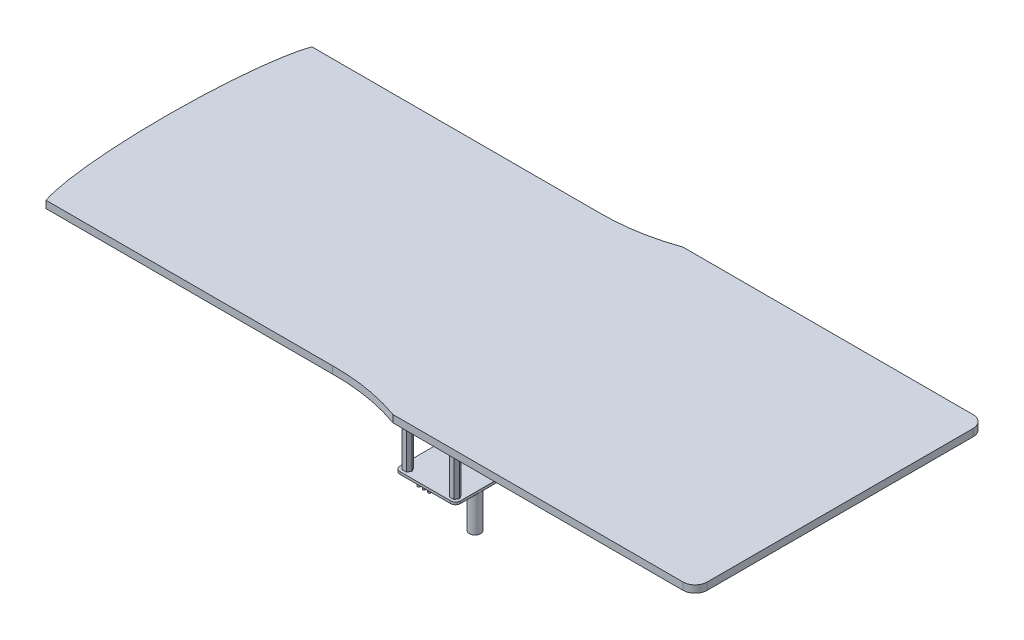
SolidWorks part; units mm, degrees
ref_plane "정면" through (0, 0, 0) normal (0, 0, 1) x (1, 0, 0)
ref_plane "윗면" through (0, 0, 0) normal (0, 1, 0) x (1, 0, 0)
ref_plane "우측면" through (0, 0, 0) normal (1, 0, 0) x (0, 0, -1)
sketch "스케치1" plane through (0, 0, 0) normal (0, 1, 0) x (1, 0, 0)
  line L1 (-140, 60) -> (140, 60)
  line L2 (-140, 60) -> (-140, -60)
  line L3 (-140, -60) -> (140, -60)
  line L4 (140, 60) -> (140, -60)
  line L5 (-140, 60) -> (140, -60) construction
  line L6 (-140, -60) -> (140, 60) construction
  point P0 (0, 0)
  dimension "D1" = 280
  dimension "D2" = 120
extrude "보스-돌출1" add sketch "스케치1" along normal blind 3
sketch "스케치2" plane through (0, 3, 0) normal (0, 1, 0) x (1, 0, 0)
  line L0 (-140, 60) -> (-130, 60)
  line L1 (140, 60) -> (-140, 60) construction
  line L2 (-130, 60) -> (-130, -60) construction
  line L3 (-140, -60) -> (140, -60) construction
  line L4 (-140, 60) -> (-140, 0)
  line L5 (-140, 0) -> (-140, -60)
  line L6 (-140, -60) -> (-130, -60)
  ellipse E0 centre (-130, 0) end of major axis (-130, -60) minor radius 9
  line M2 (140, 60) -> (-140, 60)
  line M3 (-140, 60) -> (-140, -60)
  line M4 (-140, -60) -> (140, -60)
  dimension "D1" = 10
  dimension "D2" = 9
extrude "컷-돌출1" cut sketch "스케치2" against normal blind 3 contours E0 M2 M3 M4 region at (-135, 3, -58.7958)
sketch "스케치3" plane through (0, 3, 0) normal (0, 1, 0) x (1, 0, 0)
  line L0 (140, 60) -> (-130, 60) construction
  line L1 (140, -60) -> (15, -60)
  line L2 (140, -60) -> (140, 60)
  line L3 (140, 60) -> (15, 60)
  line L4 (15, -60) -> (15, 60)
  line L5 (140, 0) -> (-65.3551, 0) construction
  line L6 (15, -60) -> (-15, -60)
  line L7 (-130, -60) -> (140, -60) construction
  line L8 (15, 60) -> (-15, 60)
  line L9 (-15, -60) -> (-15, -55)
  line L10 (-15, 60) -> (-15, 55)
  line L11 (-15, -55) -> (-133.5969, -55)
  line L12 (-15, 55) -> (-133.5969, 55)
  ellipse E0 centre (-130, 0) end of major axis (-130, -60) minor radius 9 (-130, 60) -> (-130, -60) ccw construction
  spline S0 degree 2 poles (-15, 55) (0.4381, 54.8504) (15, 60) knots 0 0 0 1 1 1
  spline S1 degree 2 poles (-15, -55) (0.4381, -54.8504) (15, -60) knots 0 0 0 1 1 1
  line M6 (140, 60) -> (-130, 60)
  ellipse M7 centre (-130, 0) end of major axis (-130, -60) minor radius 9 (-130, 60) -> (-130, -60) ccw
  line M8 (-130, -60) -> (140, -60)
  dimension "D1" = 125
  dimension "D2" = 30
  dimension "D3" = 5
extrude "컷-돌출2" cut sketch "스케치3" against normal blind 3 contours L9 L11 M7 M8 | L12 L10 M6 M7 region at (-73.7124, 3, 57.4899) region at (-73.7124, 3, -57.4899)
extrude "컷-돌출3" cut sketch "스케치3<4>" against normal blind 3 contours L10 S0 M6 | S1 L9 M8 region at (-3.645, 3, 57.9703) region at (-3.645, 3, -57.9703)
sketch "스케치3<4>" plane through (0, 3, 0) normal (0, 1, 0) x (1, 0, 0) same geometry as "스케치3"
sketch "스케치4" plane through (0, 3, 0) normal (0, 1, 0) x (1, 0, 0)
  line L0 (140, 0) -> (-139, 0) construction
  line L1 (140, -60) -> (140, 60) construction
  line L2 (140, 60) -> (140, -60)
  line L3 (140, 60) -> (74.6716, 60)
  line L4 (140, 60) -> (15, 60) construction
  line L5 (140, -60) -> (74.6716, -60)
  circle A0 centre (135, 55) radius 5
  circle A1 centre (135, -55) radius 5
  ellipse E0 centre (-130, 0) end of major axis (-130, -60) minor radius 9 (-133.5969, 55) -> (-133.5969, -55) ccw construction
  line M11 (140, -60) -> (140, 60)
  line M12 (140, 60) -> (15, 60)
  dimension "D1" = 10
  dimension "D2" = 10
extrude "컷-돌출4" cut sketch "스케치4" against normal through all contours A0 L2 M12 | A1 L5 M11 region at (138.8832, 3, 58.8832) region at (138.8832, 3, -58.8832)
sketch "스케치5" plane through (-8.1057, 0, 0) normal (0, -1, 0) x (-1, 0, 0)
  line L1 (-14.9611, -51) -> (-39.9611, -51) construction
  line L2 (-14.9611, -51) -> (-14.9611, 10) construction
  line L3 (-14.9611, 10) -> (-39.9611, 10) construction
  line L4 (-39.9611, -51) -> (-39.9611, 10) construction
  line L5 (-27.4611, 10) -> (-27.4611, -51) construction
  line L6 (-16.7613, 8.8734) -> (-15.8952, 7.3734)
  line L7 (-39.027, 7.3734) -> (-38.161, 5.8734)
  line L8 (-38.161, 5.8734) -> (-36.4289, 5.8734)
  line L9 (-36.4289, 5.8734) -> (-35.5629, 7.3734)
  line L10 (-35.5629, 7.3734) -> (-36.4289, 8.8734)
  line L11 (-36.4289, 8.8734) -> (-38.161, 8.8734)
  line L12 (-38.161, 8.8734) -> (-39.027, 7.3734)
  line L13 (-18.4933, 8.8734) -> (-16.7613, 8.8734)
  line L14 (-19.3593, 7.3734) -> (-18.4933, 8.8734)
  line L15 (-18.4933, 5.8734) -> (-19.3593, 7.3734)
  line L16 (-16.7613, 5.8734) -> (-18.4933, 5.8734)
  line L17 (-15.8952, 7.3734) -> (-16.7613, 5.8734)
  line L18 (-39.9611, -20.5) -> (-14.9611, -20.5) construction
  line L19 (-15.8952, -48.3734) -> (-16.7613, -46.8734)
  line L20 (-16.7613, -46.8734) -> (-18.4933, -46.8734)
  line L21 (-18.4933, -46.8734) -> (-19.3593, -48.3734)
  line L22 (-19.3593, -48.3734) -> (-18.4933, -49.8734)
  line L23 (-18.4933, -49.8734) -> (-16.7613, -49.8734)
  line L24 (-38.161, -49.8734) -> (-39.027, -48.3734)
  line L25 (-36.4289, -49.8734) -> (-38.161, -49.8734)
  line L26 (-35.5629, -48.3734) -> (-36.4289, -49.8734)
  line L27 (-36.4289, -46.8734) -> (-35.5629, -48.3734)
  line L28 (-38.161, -46.8734) -> (-36.4289, -46.8734)
  line L29 (-39.027, -48.3734) -> (-38.161, -46.8734)
  line L30 (-16.7613, -49.8734) -> (-15.8952, -48.3734)
  circle A0 centre (-37.2949, 7.3734) radius 1.5 construction
  circle A1 centre (-17.6273, 7.3734) radius 1.5 construction
  circle A2 centre (-17.6273, -48.3734) radius 1.5 construction
  circle A3 centre (-37.2949, -48.3734) radius 1.5 construction
  dimension "D4" = 3
  dimension "D1" = 25
  dimension "D2" = 61
extrude "보스-돌출2" add sketch "스케치5" along normal blind 25
sketch "스케치6" plane through (-8.1057, -25, 0) normal (0, -1, 0) x (1, 0, 0)
  line L1 (14.9611, 51) -> (39.9611, 51)
  line L2 (14.9611, 51) -> (14.9611, -10)
  line L3 (14.9611, -10) -> (39.9611, -10)
  line L4 (39.9611, 51) -> (39.9611, -10)
extrude "보스-돌출3" add sketch "스케치6" along normal blind 1
sketch "스케치7" plane through (-8.1057, -26, 0) normal (0, -1, 0) x (1, 0, 0)
  line L0 (14.9611, 51) -> (14.9611, -10) construction
  line L1 (14.9611, 45.5) -> (23.643, 45.5)
  line L2 (14.9611, 45.5) -> (14.9611, -4.5)
  line L3 (14.9611, -4.5) -> (23.643, -4.5)
  line L4 (23.643, 45.5) -> (23.643, -4.5)
  line L5 (14.9611, 51) -> (39.9611, 51) construction
  line L6 (14.9611, -10) -> (39.9611, -10) construction
  dimension "D1" = 5.5
  dimension "D2" = 5.5
extrude "보스-돌출4" add sketch "스케치7" along normal blind 1
sketch "스케치8" plane through (-8.1057, -27, 0) normal (0, -1, 0) x (1, 0, 0)
  line L0 (19.3021, 45.5) -> (19.3021, -4.5) construction
  line L1 (23.643, 45.5) -> (14.9611, 45.5) construction
  line L2 (14.9611, -4.5) -> (23.643, -4.5) construction
  line L4 (23.643, -4.5) -> (23.643, 45.5) construction
  line L5 (14.9611, 18.5) -> (23.643, 18.5)
  line L6 (14.9611, 18.5) -> (14.9611, 22.5)
  line L7 (14.9611, 22.5) -> (23.643, 22.5)
  line L8 (23.643, 18.5) -> (23.643, 22.5)
  line L9 (14.9611, 18.5) -> (23.643, 22.5) construction
  line L10 (14.9611, 22.5) -> (23.643, 18.5) construction
  line L11 (14.9611, 45.5) -> (14.9611, 22.5) construction
  line L12 (23.643, 20.5) -> (14.9611, 20.5) construction
  line L13 (14.9611, 34.75) -> (23.643, 34.75)
  line L14 (14.9611, 34.75) -> (14.9611, 33.25)
  line L15 (14.9611, 33.25) -> (23.643, 33.25)
  line L16 (23.643, 34.75) -> (23.643, 33.25)
  line L17 (14.9611, 34.75) -> (23.643, 33.25) construction
  line L18 (14.9611, 33.25) -> (23.643, 34.75) construction
  line L19 (23.643, 6.25) -> (23.643, 7.75)
  line L20 (14.9611, 6.25) -> (14.9611, 7.75)
  line L21 (14.9611, 6.25) -> (23.643, 6.25)
  line L22 (14.9611, 7.75) -> (23.643, 7.75)
  point P7 (19.3021, 34)
  point P8 (19.3021, 20.5)
  dimension "D1" = 4
  dimension "D2" = 1.5
extrude "컷-돌출5" cut sketch "스케치8" against normal blind 1
sketch "스케치9" plane through (-8.1057, -27, 0) normal (0, -1, 0) x (1, 0, 0)
  line L0 (19.3021, 45.5) -> (19.3021, 34.75) construction
  line L1 (23.643, 45.5) -> (14.9611, 45.5) construction
  line L2 (23.643, 34.75) -> (14.9611, 34.75) construction
  line L3 (14.9611, 45.5) -> (19.3021, 45.5) construction
  line L4 (17.1316, 45.5) -> (17.1316, 34.75) construction
  line L5 (19.4081, 45.5) -> (23.643, 45.5) construction
  line L6 (21.5255, 45.5) -> (21.5255, 34.75) construction
  line L7 (14.9611, 45.5) -> (14.9611, 34.75) construction
  line L8 (14.9611, 43.35) -> (23.643, 43.35) construction
  line L9 (23.643, 34.75) -> (23.643, 45.5) construction
  line L10 (23.643, 41.2) -> (14.9611, 41.2) construction
  line L11 (23.643, 39.05) -> (14.9611, 39.05) construction
  line L12 (23.643, 36.6613) -> (14.9611, 36.6613) construction
  line L13 (23.643, 34.75) -> (23.643, 45.5) construction
  line L14 (14.9611, 34) -> (24.7906, 34) construction
  line L15 (14.9611, 34.75) -> (14.9611, 33.25) construction
  line L16 (14.9611, 20.5) -> (24.7906, 20.5) construction
  line L17 (14.9611, 22.5) -> (14.9611, 18.5) construction
  circle A0 centre (17.1316, 43.35) radius 0.5
  circle A1 centre (19.3021, 43.35) radius 0.5
  circle A2 centre (21.5255, 43.35) radius 0.5
  circle A3 centre (17.1316, 41.2) radius 0.5
  circle A4 centre (19.3021, 41.2) radius 0.5
  circle A5 centre (21.5255, 41.2) radius 0.5
  circle A6 centre (17.1316, 39.05) radius 0.5
  circle A7 centre (19.3021, 39.05) radius 0.5
  circle A8 centre (21.5255, 39.05) radius 0.5
  circle A9 centre (17.1316, 36.6613) radius 0.5
  circle A10 centre (19.3021, 36.6613) radius 0.5
  circle A11 centre (21.5255, 36.6613) radius 0.5
  circle A12 centre (21.5255, 31.3387) radius 0.5
  circle A13 centre (19.3021, 31.3387) radius 0.5
  circle A14 centre (17.1316, 31.3387) radius 0.5
  circle A15 centre (21.5255, 28.95) radius 0.5
  circle A16 centre (19.3021, 28.95) radius 0.5
  circle A17 centre (17.1316, 28.95) radius 0.5
  circle A18 centre (21.5255, 26.8) radius 0.5
  circle A19 centre (19.3021, 26.8) radius 0.5
  circle A20 centre (17.1316, 26.8) radius 0.5
  circle A21 centre (21.5255, 24.65) radius 0.5
  circle A22 centre (19.3021, 24.65) radius 0.5
  circle A23 centre (17.1316, 24.65) radius 0.5
  circle A24 centre (17.1316, 16.35) radius 0.5
  circle A25 centre (19.3021, 16.35) radius 0.5
  circle A26 centre (21.5255, 16.35) radius 0.5
  circle A27 centre (17.1316, 14.2) radius 0.5
  circle A28 centre (19.3021, 14.2) radius 0.5
  circle A29 centre (21.5255, 14.2) radius 0.5
  circle A30 centre (17.1316, 12.05) radius 0.5
  circle A31 centre (19.3021, 12.05) radius 0.5
  circle A32 centre (21.5255, 12.05) radius 0.5
  circle A33 centre (17.1316, 9.6613) radius 0.5
  circle A34 centre (19.3021, 9.6613) radius 0.5
  circle A35 centre (21.5255, 9.6613) radius 0.5
  circle A36 centre (21.5255, 4.3387) radius 0.5
  circle A37 centre (19.3021, 4.3387) radius 0.5
  circle A38 centre (17.1316, 4.3387) radius 0.5
  circle A39 centre (21.5255, 1.95) radius 0.5
  circle A40 centre (19.3021, 1.95) radius 0.5
  circle A41 centre (17.1316, 1.95) radius 0.5
  circle A42 centre (21.5255, -0.2) radius 0.5
  circle A43 centre (19.3021, -0.2) radius 0.5
  circle A44 centre (17.1316, -0.2) radius 0.5
  circle A45 centre (21.5255, -2.35) radius 0.5
  circle A46 centre (19.3021, -2.35) radius 0.5
  circle A47 centre (17.1316, -2.35) radius 0.5
  point P29 (17.1316, 43.35)
  point P30 (17.1316, 41.2)
  point P31 (17.1316, 43.35)
  point P32 (17.1316, 43.35)
  point P33 (17.1316, 39.05)
  point P35 (17.1316, 36.6613)
  point P36 (19.3021, 43.35)
  point P37 (19.3021, 41.2)
  point P38 (19.3021, 39.05)
  point P39 (19.3021, 36.6613)
  point P40 (21.5255, 43.35)
  point P41 (21.5255, 41.2)
  point P42 (21.5255, 39.05)
  point P43 (21.5255, 36.6613)
  point P95 (17.1316, 24.65)
  point P96 (17.1316, 24.65)
  point P149 (17.1316, 16.35)
  point P150 (17.1316, 16.35)
  point P151 (17.1316, -2.35)
  point P152 (17.1316, -2.35)
  dimension "D1" = 2.15
  dimension "D2" = 2.15
  dimension "D3" = 2.15
  dimension "D4" = 2.3887
extrude "보스-돌출5" add sketch "스케치9" along normal blind 7
sketch "스케치10" plane through (-8.1057, -26, 0) normal (0, -1, 0) x (1, 0, 0)
  line L0 (14.9611, 20.5) -> (39.9611, 20.5) construction
  line L1 (14.9611, 22.5) -> (14.9611, 18.5) construction
  line L2 (39.9611, -10) -> (39.9611, 51) construction
  line L3 (27.4611, 51) -> (27.4611, -10) construction
  line L4 (39.9611, 51) -> (14.9611, 51)
  line L5 (39.9611, 51) -> (39.9611, -10)
  line L6 (39.9611, -10) -> (14.9611, -10)
  line L7 (14.9611, 51) -> (14.9611, -10)
  arc A0 (39.9611, 49) -> (37.9611, 51) centre (37.9611, 49) ccw
  arc A1 (14.9611, 49) -> (16.9611, 51) centre (16.9611, 49) cw
  arc A2 (14.9611, -8) -> (16.9611, -10) centre (16.9611, -8) ccw
  arc A3 (39.9611, -8) -> (37.9611, -10) centre (37.9611, -8) cw
  line M21 (14.9611, -10) -> (39.9611, -10)
  line M22 (39.9611, -10) -> (39.9611, 51)
  line M23 (39.9611, 51) -> (14.9611, 51)
  line M24 (14.9611, 51) -> (14.9611, 45.5)
extrude "컷-돌출6" cut sketch "스케치10" against normal blind 7 contours A2 L7 M21 | A3 M22 M21 | A0 L5 M23 | A1 M24 M23 region at (31.4087, -26, 50.5533) region at (7.3022, -26, 50.5533) region at (31.4087, -26, -9.5533) region at (7.3022, -26, -9.5533)
sketch "스케치11" plane through (-8.1057, -26, 0) normal (0, -1, 0) x (1, 0, 0)
  line L0 (23.643, 22.5) -> (39.9611, 22.5) construction
  line L1 (39.9611, -8) -> (39.9611, 49) construction
  line L2 (23.643, 18.5) -> (39.9611, 18.5) construction
  line L4 (39.9611, 22.5) -> (34.9611, 22.5)
  line L5 (39.9611, 22.5) -> (39.9611, 18.5)
  line L6 (39.9611, 18.5) -> (34.9611, 18.5)
  line L7 (34.9611, 22.5) -> (34.9611, 18.5)
  dimension "D1" = 5
extrude "보스-돌출6" add sketch "스케치11" along normal blind 8
sketch "스케치12" plane through (-8.1057, 0, 22.5) normal (0, 0, 1) x (1, 0, 0)
  line L0 (37.4611, -34) -> (37.4611, -26) construction
  line L1 (39.9611, -34) -> (34.9611, -34) construction
  line L2 (39.9611, -26) -> (34.9611, -26) construction
  line L3 (36.4492, -34) -> (38.4731, -34)
  line L4 (38.4731, -34) -> (39.9611, -32.359)
  line L5 (39.9611, -34) -> (39.9611, -26) construction
  line L6 (36.4492, -34) -> (34.9611, -32.359)
  line L8 (34.9611, -32.359) -> (34.9611, -34)
  line L9 (34.9611, -34) -> (36.4492, -34)
  line L10 (38.4731, -34) -> (39.9611, -34)
  line L11 (39.9611, -34) -> (39.9611, -32.359)
  line M7 (34.9611, -26) -> (34.9611, -34)
  line M8 (34.9611, -34) -> (39.9611, -34)
  line M9 (39.9611, -34) -> (39.9611, -26)
extrude "컷-돌출7" cut sketch "스케치12" against normal blind 8 contours L6 M8 M7 | L4 M8 M9 region at (31.3594, -33.453, 22.5) region at (27.3515, -33.453, 22.5)
sketch "스케치13" plane through (-8.1057, -34, 0) normal (0, -1, 0) x (1, 0, 0)
  line L0 (36.4492, 20.5) -> (38.4731, 20.5) construction
  line L1 (36.4492, 22.5) -> (36.4492, 18.5) construction
  line L2 (38.4731, 22.5) -> (38.4731, 18.5) construction
  circle A0 centre (37.4611, 21.5) radius 0.5
  circle A1 centre (37.4611, 19.5) radius 0.5
  dimension "D1" = 2
extrude "컷-돌출8" cut sketch "스케치13" against normal blind 2
sketch "스케치14" plane through (31.8555, 0, 0) normal (1, 0, 0) x (0, 0, -1)
  line L0 (-22.5, -26) -> (-18.5, -26) construction
  line L1 (-20.5, -26) -> (-20.5, -29.4126) construction
  line L2 (-19.0408, -26.1757) -> (-19.0408, -28.1757)
  line L3 (-21.9592, -26.1757) -> (-20.9592, -26.1757)
  line L4 (-21.9592, -26.1757) -> (-21.9592, -28.1757)
  line L5 (-21.9592, -28.1757) -> (-20.9592, -28.1757)
  line L6 (-20.9592, -26.1757) -> (-20.9592, -28.1757)
  line L7 (-19.0408, -26.1757) -> (-20.0408, -26.1757)
  line L8 (-20.0408, -26.1757) -> (-20.0408, -28.1757)
  line L9 (-19.0408, -28.1757) -> (-20.0408, -28.1757)
  dimension "D1" = 1
  dimension "D2" = 2
extrude "컷-돌출9" cut sketch "스케치14" against normal blind 2
sketch "스케치15" plane through (-8.1057, -26, 0) normal (0, -1, 0) x (1, 0, 0)
  line L0 (39.9611, 22.5) -> (39.9611, 49) construction
  circle A0 centre (37.6395, 40.5947) radius 2.3216
extrude "보스-돌출7" add sketch "스케치15" along normal blind 15
